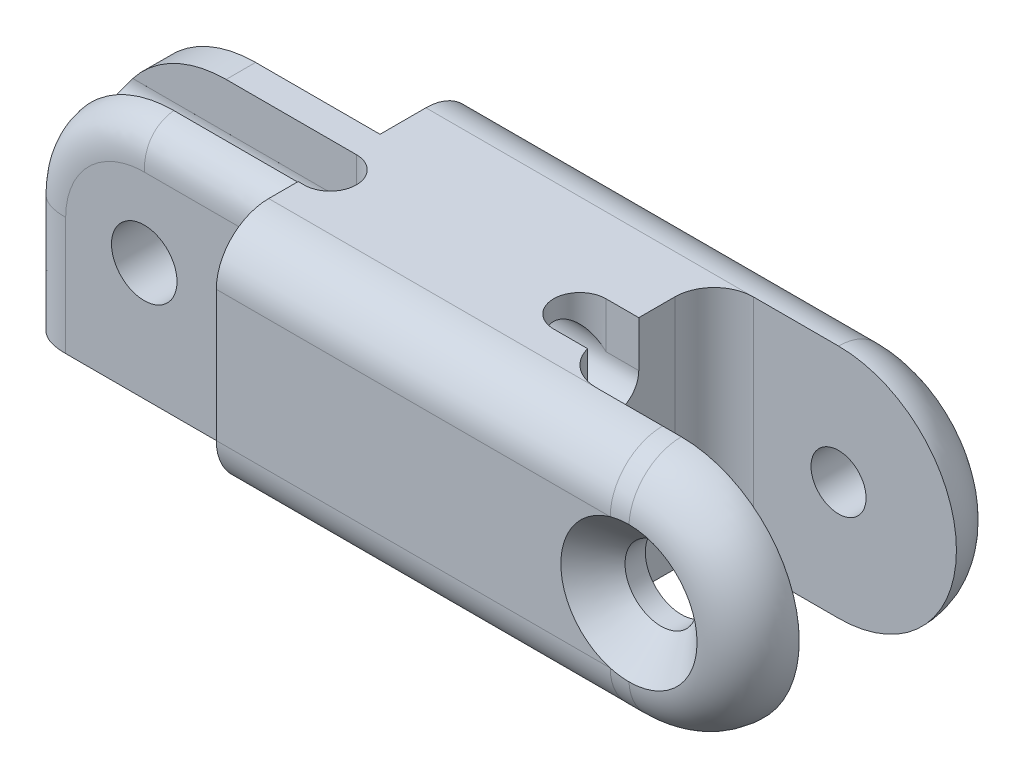
SolidWorks part; units mm, degrees
ref_plane "Front Plane" through (0, 0, 0) normal (0, 0, 1) x (1, 0, 0)
ref_plane "Top Plane" through (0, 0, 0) normal (0, 1, 0) x (1, 0, 0)
ref_plane "Right Plane" through (0, 0, 0) normal (1, 0, 0) x (0, 0, -1)
sketch "Sketch2" plane through (0, 0, 0) normal (0, 1, 0) x (1, 0, 0)
  line L0 (-11, 10) -> (29.5, 10)
  line L1 (29.5, 10) -> (29.5, 6)
  line L2 (29.5, 6) -> (14, 6)
  line L3 (11, 3) -> (11, -3)
  line L4 (14, -6) -> (29.5, -6)
  line L5 (29.5, -6) -> (29.5, -10)
  line L7 (-29.5, -6) -> (-29.5, 2.5)
  line L8 (-49.3622, 0) -> (56.3776, 0) construction
  line L9 (0, 21.2372) -> (0, -19.0689) construction
  line L10 (11, 3) -> (14, 3) construction
  line L11 (14, 3) -> (14, 6) construction
  line L16 (-11, -10) -> (29.5, -10)
  line L18 (-29.5, -6) -> (-11, -6)
  line L19 (-11, -6) -> (-11, -10)
  line L20 (-29.5, 2.5) -> (-11, 2.5)
  line L21 (-11, 2.5) -> (-11, 10)
  arc A0 (14, 6) -> (11, 3) centre (14, 3) ccw
  arc A1 (14, -6) -> (11, -3) centre (14, -3) cw
  point P13 (14, 3)
  dimension "D1" = 59
  dimension "D2" = 20
  dimension "D3" = 4
  dimension "D4" = 18.5
  dimension "D5" = 12
  dimension "D6" = 3
  dimension "D7" = 3
  dimension "D8" = 7.5
  dimension "D9" = 4
  dimension "D10" = 8.5
  dimension "D11" = 18.5
extrude "Boss-Extrude1" add sketch "Sketch2" along normal blind 18
sketch "Sketch5" plane through (0, 0, 10) normal (0, 0, 1) x (1, 0, 0)
  line L0 (-29.5, 9) -> (31.8491, 9) construction
  line L1 (-20.5, 18) -> (-20.5, 0) construction
  line L2 (29.5, 18) -> (29.5, 0) construction
  line L3 (-11, 18) -> (29.5, 18) construction
  line L4 (20.5, 18) -> (20.5, 0) construction
  line L5 (-29.5, 18) -> (-29.5, 0) construction
  line L6 (-29.5, 9) -> (-29.5, 0)
  line L7 (-29.5, 18) -> (-11, 18) construction
  line L8 (-29.5, 0) -> (20.5, 0)
  line L9 (-20.5, 18) -> (20.5, 18)
  arc A0 (-20.5, 18) -> (-29.5, 9) centre (-20.5, 9) ccw
  arc A1 (20.5, 0) -> (20.5, 18) centre (20.5, 9) ccw
  circle A2 centre (-20.5, 9) radius 2.5
  dimension "D2" = 5
  dimension "D1" = 9
extrude "Cut-Extrude1" cut sketch "Sketch5" against normal blind 20 flip side to cut
sketch "Sketch6" plane through (0, 0, 10) normal (0, 0, 1) x (1, 0, 0)
  line L0 (20.5, 0) -> (20.5, 18) construction
  point P4 (20.5, 9)
hole_wizard "CSK for M5 Countersunk Flat Head Screw1" positions "Sketch7" profile "Sketch8" countersink size "M5" standard "DIN" end condition up to next
sketch "Sketch7" plane through (0, 0, 10) normal (0, 0, 1) x (1, 0, 0)
  point P0 (20.5, 9)
sketch "Sketch8" plane through (20.5, 9, 10) normal (1, 0, 0) x (0, -1, 0)
  line L0 (0, 0) -> (0, 4)
  line L1 (0, 4) -> (2.75, 4)
  line L2 (2.75, 4) -> (2.75, 2.45)
  line L3 (2.75, 2.45) -> (5.2, 0)
  line L5 (5.2, 0) -> (0, 0)
  line L6 (-2.75, 2.45) -> (-5.2, 0) construction
  line L11 (0, -6.35) -> (0, 107.95) construction
  dimension "Thru Hole Dia." = 5.5
  dimension "Thru Hole Depth" = 4
  dimension "Near C'Sink Dia." = 10.4
  dimension "Near C'Sink Angle" = 90
hole_wizard "M5 Tapped Hole1" positions "Sketch9" profile "Sketch11" tap size "M5" standard "DIN" end condition through all
sketch "Sketch9" plane through (0, 0, 10) normal (0, 0, 1) x (1, 0, 0)
  point P0 (20.5, 9)
sketch "Sketch11" plane through (20.5, 9, 10) normal (1, 0, 0) x (0, -1, 0)
  line L0 (0, 0) -> (0, 20)
  line L1 (0, 20) -> (2.1, 20)
  line L2 (2.1, 20) -> (2.1, 3.1)
  line L3 (2.1, 3.1) -> (5.2, 0)
  line L5 (5.2, 0) -> (0, 0)
  line L6 (-2.1, 3.1) -> (-5.2, 0) construction
  line L11 (0, -6.35) -> (0, 107.95) construction
  dimension "Thru Tap Drill Dia." = 4.2
  dimension "Thru Tap Drill Depth" = 20
  dimension "Near C'Sink Dia." = 10.4
  dimension "Near C'Sink Angle" = 90
cosmetic thread "Hole Thread1" parameters "D2"=5
fillet "Fillet1" radius 4 2 edges at (4.75, 0, 10) (4.75, 18, 10)
fillet "Fillet2" radius 4 3 edges at (4.75, 0, -10) (29.5, 9, -10) (4.75, 18, -10)
fillet "Fillet3" radius 3 3 edges at (-29.5, 4.5, 6) (-15.75, 18, 6) (-26.864, 15.364, 6) conic rho 0.5
sketch "Sketch13" plane through (11, 0, 0) normal (1, 0, 0) x (0, 0, -1)
  line L0 (-1.75, 21.4915) -> (-1.75, -4.5302) construction
  line L1 (-3, 18) -> (3, 18) construction
  circle A0 centre (-1.75, 14.5) radius 2
  dimension "D2" = 4
  dimension "D3" = 3.5
  dimension "D1" = 1.75
extrude "Cut-Extrude2" cut sketch "Sketch13" against normal through all both and the other way through all
sketch "Sketch14" plane through (0, 18, 0) normal (0, 1, 0) x (1, 0, 0)
  line L0 (-27.6236, 0.2504) -> (-10.5557, 0.2504)
  line L1 (-27.5557, -3.75) -> (-10.5557, -3.75)
  line L3 (-27.5557, -3.75) -> (-27.6236, 0.2504)
  arc A0 (-10.5557, -3.75) -> (-10.5557, 0.2504) centre (-10.5557, -1.7498) ccw
  spline S1 degree 3 poles (-26.0797, -3) (-25.9473, -2.8693) (-25.8242, -2.7233) (-25.6669, -2.4679) (-25.62, -2.3776) (-25.5431, -2.1872) (-25.5127, -2.0851) (-25.4764, -1.8774) (-25.4703, -1.7698) (-25.4841, -1.5572) (-25.5036, -1.4537) (-25.5944, -1.1509) (-25.6934, -0.9724) (-25.9222, -0.6565) (-26.0506, -0.5207) (-26.3219, -0.2789) (-26.4619, -0.1762) (-26.8834, 0.0849) (-27.1717, 0.1991) (-27.5706, 0.2557) (-27.7006, 0.2556) (-27.9459, 0.209) (-28.0594, 0.1634) (-28.269, 0.0188) (-28.3624, -0.0793) (-28.5226, -0.3256) (-28.5911, -0.4779) (-28.6703, -0.7331) (-28.6932, -0.8231) (-28.7322, -1.0133) (-28.7481, -1.1133) (-28.7724, -1.3157) (-28.781, -1.419) (-28.7912, -1.6301) (-28.7926, -1.7379) (-28.7863, -2.055) (-28.7677, -2.2665) (-28.7021, -2.6575) (-28.6546, -2.8399) (-28.5922, -3) knots 0 0 0 0 0.0625 0.0625 0.09375 0.09375 0.125 0.125 0.15625 0.15625 0.1875 0.1875 0.25 0.25 0.3125 0.3125 0.375 0.375 0.5 0.5 0.5625 0.5625 0.625 0.625 0.6875 0.6875 0.75 0.75 0.78125 0.78125 0.8125 0.8125 0.84375 0.84375 0.875 0.875 0.9375 0.9375 1 1 1 1 construction
  spline S2 degree 3 poles (-28.5922, -3) (-28.5381, -3.1387) (-28.4701, -3.2552) (-28.3108, -3.4526) (-28.2195, -3.5323) (-28.0254, -3.6532) (-27.9205, -3.6957) (-27.705, -3.7461) (-27.594, -3.7546) (-27.2507, -3.7337) (-27.0173, -3.6588) (-26.5422, -3.4019) (-26.3092, -3.2263) (-26.0797, -3) knots 0 0 0 0 0.125 0.125 0.25 0.25 0.375 0.375 0.5 0.5 0.75 0.75 1 1 1 1 construction
  dimension "D2" = 2.0002
  dimension "D1" = 17
extrude "Cut-Extrude3" cut sketch "Sketch14" against normal blind 3.5
sketch "Sketch15" plane through (0, 18, 0) normal (0, 1, 0) x (1, 0, 0)
sketch "Sketch16" plane through (0, 18, 0) normal (0, 1, 0) x (1, 0, 0)
  line L0 (-8.0769, -1.75) -> (29.6251, -1.75) construction
  line L1 (8.5, 0.25) -> (19.0559, 0.25)
  line L3 (8.5, -3.75) -> (19.0559, -3.75)
  line L4 (19.0559, 0.25) -> (19.0559, -3.75)
  line L5 (11, -3) -> (11, 3) construction
  arc A0 (8.5, 0.25) -> (8.5, -3.75) centre (8.5, -1.75) ccw
  dimension "D2" = 4
  dimension "D1" = 1.75
  dimension "D3" = 2.5
extrude "Cut-Extrude4" cut sketch "Sketch16" against normal blind 3.5
